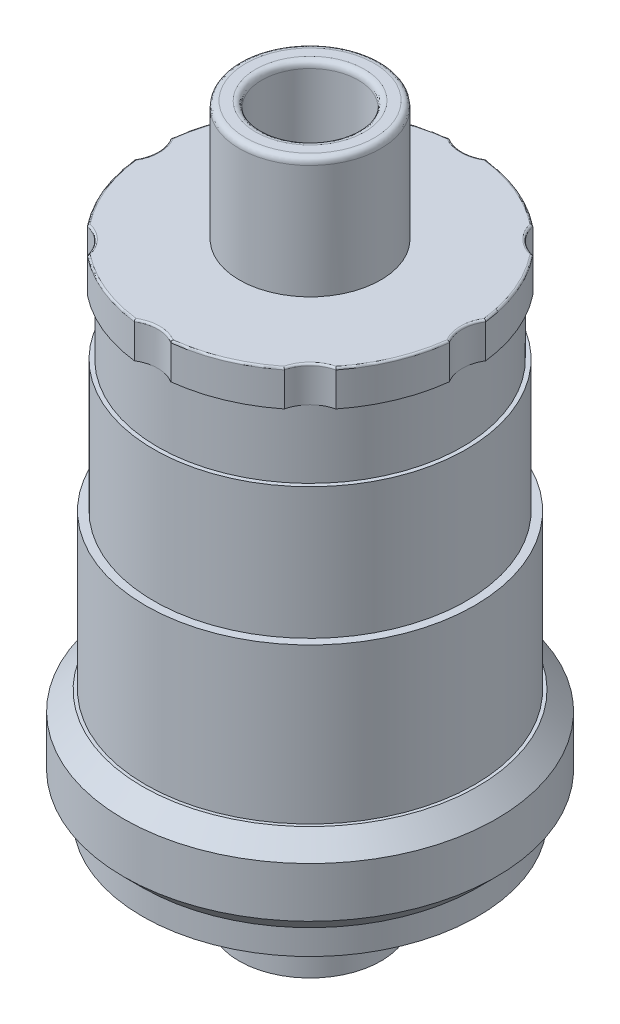
SolidWorks part; units mm, degrees
ref_plane "Front Plane" through (0, 0, 0) normal (0, 0, 1) x (1, 0, 0)
ref_plane "Top Plane" through (0, 0, 0) normal (0, 1, 0) x (1, 0, 0)
ref_plane "Right Plane" through (0, 0, 0) normal (1, 0, 0) x (0, 0, -1)
sketch "Sketch1" plane through (0, 0, 0) normal (1, 0, 0) x (0, 0, -1)
  line L0 (0, 19.2318) -> (0, -17.608) construction
  line L1 (0, -13.9545) -> (11.35, -13.9545)
  line L2 (11.35, -13.9545) -> (11.35, -0.0545)
  line L3 (0, -0.0545) -> (0, -8.2545)
  line L4 (0, -13.9545) -> (0, -8.2545)
  line L17 (11.35, -0.0545) -> (0, -0.0545) construction
  line L18 (10.25, -8.2545) -> (0, -8.2545)
  line L19 (10.25, -13.9545) -> (10.25, -8.2545)
  line L20 (11.35, -0.0545) -> (0, -0.0545)
  line L21 (0, -0.0545) -> (11.35, -0.0545)
  dimension "D1" = 10.25
  dimension "D2" = 13.9
  dimension "D4" = 5.7
  dimension "D5" = 1.1
revolve "Revolve1" add sketch "Sketch1" angle 360 about L0 region at (0, -4.5931, -5.9985)
sketch "Sketch2" plane through (0, -8.2545, 0) normal (0, -1, 0) x (1, 0, 0)
  line L0 (0, 10.25) -> (0, -10.25) construction
  line L1 (-10.25, 0) -> (10.25, 0) construction
  circle A0 centre (0, 0) radius 3.3
  circle A1 centre (0, 0) radius 10.25 construction
  circle A2 centre (0, 0) radius 10.25 construction
  circle A3 centre (0, 6.6954) radius 1.9
  circle A4 centre (4.7344, 4.7344) radius 1.9
  circle A5 centre (6.6954, 0) radius 1.9
  circle A6 centre (4.7344, -4.7344) radius 1.9
  circle A7 centre (0, -6.6954) radius 1.9
  circle A8 centre (-4.7344, -4.7344) radius 1.9
  circle A9 centre (-6.6954, 0) radius 1.9
  circle A10 centre (-4.7344, 4.7344) radius 1.9
  point P31 (0, 0)
  dimension "D1" = 6.6
  dimension "D2" = 3.8
  dimension "D3" = 8
extrude "Cut-Extrude1" cut sketch "Sketch2" against normal blind 5
sketch "Sketch5" plane through (0, -0.0545, 0) normal (0, 1, 0) x (1, 0, 0)
  circle A0 centre (0, 0) radius 26.8
  dimension "D1" = 53.6
extrude "Boss-Extrude3" add sketch "Sketch5" along normal blind 4
sketch "Sketch7" plane through (0, 3.9455, 0) normal (0, 1, 0) x (1, 0, 0)
  circle A0 centre (0, 0) radius 26.8
  point P3 (0, 0)
extrude "Boss-Extrude4" add sketch "Sketch7" along normal blind 3 draft 45 draft outward yes
sketch "Sketch8" plane through (0, 6.9455, 0) normal (0, 1, 0) x (1, 0, 0)
  circle A0 centre (0, 0) radius 29.8
extrude "Boss-Extrude5" add sketch "Sketch8" along normal blind 8
sketch "Sketch9" plane through (0, 14.9455, 0) normal (0, 1, 0) x (1, 0, 0)
  circle A0 centre (0, 0) radius 29.8
extrude "Boss-Extrude6" add sketch "Sketch9" along normal blind 3 draft 45
sketch "Sketch10" plane through (0, 17.9455, 0) normal (0, 1, 0) x (1, 0, 0)
  circle A0 centre (0, 0) radius 26.3
  dimension "D1" = 52.6
extrude "Boss-Extrude7" add sketch "Sketch10" along normal blind 24.8
sketch "Sketch11" plane through (0, 42.7455, 0) normal (0, 1, 0) x (1, 0, 0)
  circle A1 centre (0, 0) radius 25
  dimension "D1" = 50
extrude "Boss-Extrude8" add sketch "Sketch11" along normal blind 21
sketch "Sketch12" plane through (0, 63.7455, 0) normal (0, 1, 0) x (1, 0, 0)
  circle A0 centre (0, 0) radius 24.35
  dimension "D1" = 48.7
extrude "Boss-Extrude9" add sketch "Sketch12" along normal blind 10.9
sketch "Sketch13" plane through (0, 74.6455, 0) normal (0, 1, 0) x (1, 0, 0)
  arc A0 (-19.8613, 15.7528) -> (-25.183, 2.9052) centre (0, 0) ccw
  arc A2 (-2.9052, 25.183) -> (2.9052, 25.183) centre (0, 29.8328) ccw
  arc A3 (15.7528, 19.8613) -> (19.8613, 15.7528) centre (21.095, 21.095) ccw
  arc A4 (25.183, 2.9052) -> (25.183, -2.9052) centre (29.8328, 0) ccw
  arc A5 (19.8613, -15.7528) -> (15.7528, -19.8613) centre (21.095, -21.095) ccw
  arc A6 (2.9052, -25.183) -> (-2.9052, -25.183) centre (0, -29.8328) ccw
  arc A7 (-15.7528, -19.8613) -> (-19.8613, -15.7528) centre (-21.095, -21.095) ccw
  arc A8 (-25.183, -2.9052) -> (-25.183, 2.9052) centre (-29.8328, 0) ccw
  arc A9 (-19.8613, 15.7528) -> (-15.7528, 19.8613) centre (-21.095, 21.095) ccw
  arc A16 (-25.183, -2.9052) -> (-19.8613, -15.7528) centre (0, 0) ccw
  arc A17 (-15.7528, -19.8613) -> (-2.9052, -25.183) centre (0, 0) ccw
  arc A18 (2.9052, -25.183) -> (15.7528, -19.8613) centre (0, 0) ccw
  arc A19 (19.8613, -15.7528) -> (25.183, -2.9052) centre (0, 0) ccw
  arc A20 (25.183, 2.9052) -> (19.8613, 15.7528) centre (0, 0) ccw
  arc A21 (15.7528, 19.8613) -> (2.9052, 25.183) centre (0, 0) ccw
  arc A22 (-2.9052, 25.183) -> (-15.7528, 19.8613) centre (0, 0) ccw
  point P22 (0, 0)
  dimension "D1" = 50.7
  dimension "D2" = 8
extrude "Boss-Extrude11" add sketch "Sketch13" along normal blind 5.7
fillet "Fillet1" radius 0.3 16 edges at (-24.35, 80.3455, 0) (-23.4203, 80.3455, 9.701) (-17.2181, 80.3455, 17.2181) (-9.701, 80.3455, 23.4203) (0, 80.3455, 24.35) (9.701, 80.3455, 23.4203) (17.2181, 80.3455, 17.2181) (23.4203, 80.3455, 9.701) (24.35, 80.3455, 0) (23.4203, 80.3455, -9.701) (17.2181, 80.3455, -17.2181) (9.701, 80.3455, -23.4203) (0, 80.3455, -24.35) (-9.701, 80.3455, -23.4203) (-17.2181, 80.3455, -17.2181) (-23.4203, 80.3455, -9.701)
sketch "Sketch15" plane through (0, 80.3455, 0) normal (0, 1, 0) x (1, 0, 0)
  circle A0 centre (0, 0) radius 11.3
  dimension "D1" = 22.6
extrude "Boss-Extrude12" add sketch "Sketch15" along normal blind 19.2
sketch "Sketch17" plane through (0, 99.5455, 0) normal (0, 1, 0) x (1, 0, 0)
  circle A0 centre (0, 0) radius 7.7
  dimension "D1" = 15.4
extrude "Cut-Extrude3" cut sketch "Sketch17" against normal blind 20.2
fillet "Fillet3" radius 1 2 edges at (0, 99.5455, 7.7) (0, 99.5455, 11.3) conic rho 0.5
